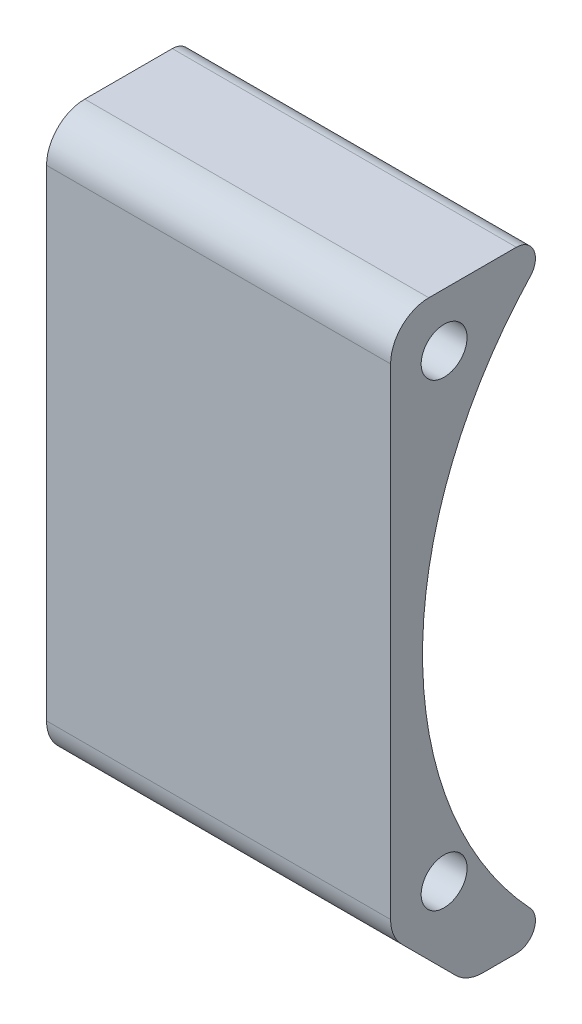
SolidWorks part; units mm, degrees
ref_plane "Front Plane" through (0, 0, 0) normal (0, 0, 1) x (1, 0, 0)
ref_plane "Top Plane" through (0, 0, 0) normal (0, 1, 0) x (1, 0, 0)
ref_plane "Right Plane" through (0, 0, 0) normal (1, 0, 0) x (0, 0, -1)
sketch "Sketch1" plane through (0, 0, 0) normal (1, 0, 0) x (0, 0, -1)
  line L0 (0, 0) -> (0, 50.8)
  line L1 (0, 50.8) -> (14.3998, 50.8)
  line L2 (0, 0) -> (14.3998, 0)
  arc A0 (14.3998, 50.8) -> (14.3998, 0) centre (35.9921, 25.4) ccw
  point P6 (35.9921, 25.4)
  dimension "D1" = 50.8
  dimension "D2" = 66.675
extrude "Boss-Extrude1" add sketch "Sketch1" along normal blind 28.575
chamfer "Chamfer1" distance 6.35 angle 45 1 edges at (14.2875, 0, 0)
fillet "Fillet1" radius 3.175 3 edges at (14.2875, 6.35, 0) (14.2875, 0, -6.35) (14.2875, 50.8, 0)
fillet "Fillet2" radius 1.5875 2 edges at (14.2875, 50.8, -14.3998) (14.2875, 0, -14.3998)
sketch "Sketch2" plane through (28.575, 0, 0) normal (1, 0, 0) x (0, 0, -1)
  line L0 (10.4437, 50.8) -> (3.175, 50.8) construction
  line L1 (0, 47.625) -> (0, 7.6651) construction
  line L2 (0.9299, 5.4201) -> (5.4201, 0.9299) construction
  circle A0 centre (4.445, 46.355) radius 4.445 construction
  circle A1 centre (4.445, 8.1912) radius 4.445 construction
  point P0 (4.445, 46.355)
  point P2 (4.445, 8.1912)
  dimension "D1" = 8.89
hole_wizard "#8 Clearance Hole1" positions "Sketch2" profile "Sketch3" hole size "#8" standard "ANSI Inch" end condition through all
sketch "Sketch3" plane through (28.575, 46.355, -4.445) normal (0, 1, 0) x (0, 0, -1)
  line L0 (0, 0) -> (0, 28.575)
  line L1 (0, 28.575) -> (1.905, 28.575)
  line L2 (1.905, 28.575) -> (1.905, 0)
  line L5 (1.905, 0) -> (0, 0)
  line L11 (0, -6.35) -> (0, 107.95) construction
  dimension "Thru Hole Dia." = 3.81
  dimension "Thru Hole Depth" = 28.575
sketch "Sketch4" plane through (0, 0, 0) normal (-1, 0, 0) x (0, 0, 1)
  line L0 (-4.445, 49.53) -> (-11.9991, 49.53)
  line L1 (-4.445, 43.18) -> (-7.7917, 43.18)
  line L2 (-4.445, 11.3662) -> (-5.7524, 11.3662)
  line L3 (-4.445, 5.0162) -> (-9.6124, 5.0162)
  arc A0 (-4.445, 43.18) -> (-4.445, 49.53) centre (-4.445, 46.355) ccw
  arc A1 (-4.445, 5.0162) -> (-4.445, 11.3662) centre (-4.445, 8.1912) ccw
  arc A2 (-11.605, 2.6699) -> (-11.605, 48.1301) centre (-35.9921, 25.4) ccw construction
  arc A3 (-9.6124, 5.0162) -> (-5.7524, 11.3662) centre (-35.9921, 25.4) ccw
  arc A4 (-10.4437, 50.8) -> (-11.605, 48.1301) centre (-10.4437, 49.2125) ccw construction
  arc A5 (-11.9991, 49.53) -> (-11.605, 48.1301) centre (-10.4437, 49.2125) ccw
  arc A6 (-7.7917, 43.18) -> (-11.605, 48.1301) centre (-35.9921, 25.4) ccw
  dimension "D1" = 6.35
extrude "Cut-Extrude1" cut sketch "Sketch4" against normal blind 6.35
sketch "Sketch5" [suppressed] plane through (28.575, 0, 0) normal (1, 0, 0) x (0, 0, -1)
  line L0 (4.7625, 49.2125) -> (13.534, 49.2125)
  line L1 (4.7625, 42.8625) -> (10.2902, 42.8625)
  line L4 (4.7625, 11.4977) -> (8.8696, 11.4977)
  line L5 (4.7625, 5.1477) -> (11.6784, 5.1477)
  arc A0 (4.7625, 49.2125) -> (4.7625, 42.8625) centre (4.7625, 46.0375) ccw
  arc A1 (4.7625, 11.4977) -> (4.7625, 5.1477) centre (4.7625, 8.3227) ccw
  arc A2 (13.2807, 48.3523) -> (11.9465, 50.8) centre (11.9465, 49.2125) ccw construction
  arc A3 (13.2807, 48.3523) -> (13.2807, 2.4477) centre (48.8816, 25.4) ccw construction
  arc A4 (13.2807, 48.3523) -> (10.2902, 42.8625) centre (48.8816, 25.4) ccw
  arc A5 (13.2807, 48.3523) -> (13.534, 49.2125) centre (11.9465, 49.2125) ccw
  arc A6 (8.8696, 11.4977) -> (11.6784, 5.1477) centre (48.8816, 25.4) ccw
  circle A7 centre (4.7625, 8.3227) radius 1.905 construction
  dimension "D1" = 6.35
extrude "Cut-Extrude2" [suppressed] cut sketch "Sketch5" against normal blind 6.35
